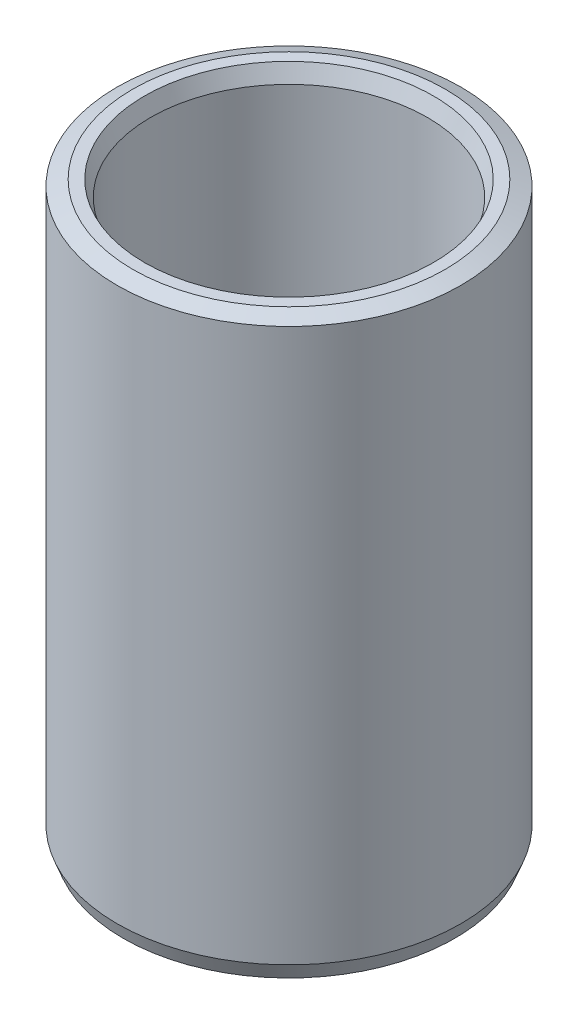
SolidWorks part; units mm, degrees
ref_plane "Front Plane" through (0, 0, 0) normal (0, 0, 1) x (1, 0, 0)
ref_plane "Top Plane" through (0, 0, 0) normal (0, 1, 0) x (1, 0, 0)
ref_plane "Right Plane" through (0, 0, 0) normal (1, 0, 0) x (0, 0, -1)
sketch "Sketch1" plane through (0, 0, 0) normal (0, 1, 0) x (1, 0, 0)
  circle A0 centre (0, 0) radius 50
  dimension "SLEEVE_OD" = 100
extrude "Boss-Extrude1" add sketch "Sketch1" along normal blind 167.1478
sketch "Sketch2" plane through (0, 0, 0) normal (0, 1, 0) x (1, 0, 0)
  circle A0 centre (0, 0) radius 40.2782
  dimension "BORE_D" = 80.5564
extrude "Cut-Extrude1" cut sketch "Sketch2" along normal through all
chamfer "Chamfer1" distance 1.7471 angle 69.009 4 edges at (0, 167.1478, 40.2782) (0, 0, 40.2782) (0, 0, 50) (0, 167.1478, 50) first distance on face at (0, 167.1478, 40.2782) first distance on face at (0, 0, 40.2782) first distance on face at (0, 167.1478, 50)
